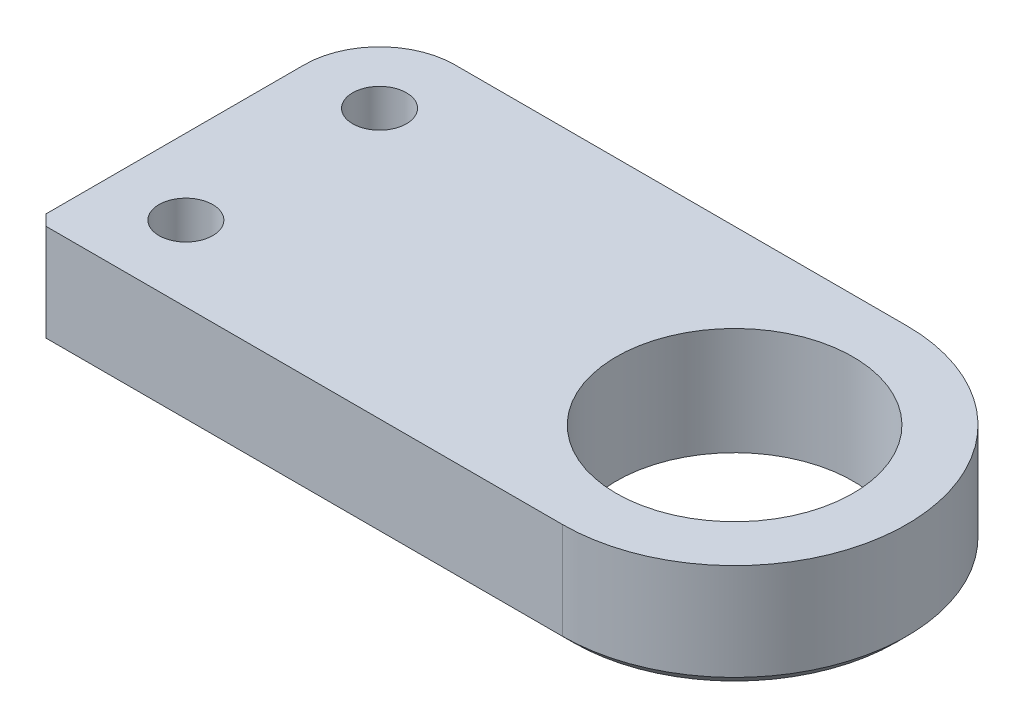
SolidWorks part; units mm, degrees
ref_plane "前视基准面" through (0, 0, 0) normal (0, 0, 1) x (1, 0, 0)
ref_plane "上视基准面" through (0, 0, 0) normal (0, 1, 0) x (1, 0, 0)
ref_plane "右视基准面" through (0, 0, 0) normal (1, 0, 0) x (0, 0, -1)
sketch "草图1" plane through (0, 0, 0) normal (0, 1, 0) x (1, 0, 0)
  line L0 (0, 16) -> (-42, 16)
  line L1 (0, -16) -> (-48, -16)
  line L2 (-49, 9) -> (-49, -15)
  line L3 (-42, 9) -> (-42, -9) construction
  line L4 (-42, 0) -> (0, 0) construction
  line L5 (-48, -16) -> (-49, -15)
  arc A0 (0, 16) -> (0, -16) centre (0, 0) cw
  circle A1 centre (0, 0) radius 11
  circle A2 centre (-42, 9) radius 2.5
  circle A3 centre (-42, -9) radius 2.5
  arc A4 (-42, 16) -> (-49, 9) centre (-42, 9) ccw
  point P5 (-49, -16)
  point P11 (-62.9079, -22.3061)
  point P12 (-31.7114, -23.2881)
  point P13 (0, 0)
  dimension "D1" = 32
  dimension "D2" = 22
  dimension "D3" = 5
  dimension "D7" = 7
  dimension "D4" = 42
  dimension "D5" = 7
  dimension "D6" = 7
extrude "凸台-拉伸1" add sketch "草图1" along normal blind 10
chamfer "倒角1" distance 1 angle 45 5 edges at (-24, 0, 16) (16, 0, 0) (-21, 0, -16) (-46.9497, 0, -13.9497) (-49, 0, 3)
